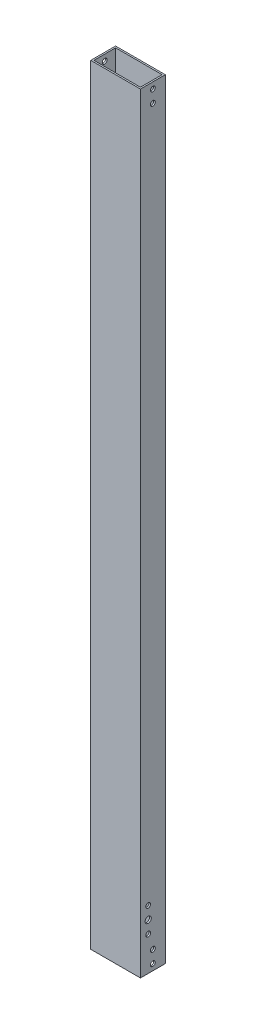
SolidWorks part; units mm, degrees
ref_plane "Front Plane" through (0, 0, 0) normal (0, 0, 1) x (1, 0, 0)
ref_plane "Top Plane" through (0, 0, 0) normal (0, 1, 0) x (1, 0, 0)
ref_plane "Right Plane" through (0, 0, 0) normal (1, 0, 0) x (0, 0, -1)
sketch "Sketch1" plane through (0, 0, 0) normal (0, 0, 1) x (1, 0, 0)
  line L1 (-25.4, -393.7) -> (25.4, -393.7)
  line L2 (-25.4, -393.7) -> (-25.4, 393.7)
  line L3 (-25.4, 393.7) -> (25.4, 393.7)
  line L4 (25.4, -393.7) -> (25.4, 393.7)
  line L5 (-25.4, -393.7) -> (25.4, 393.7) construction
  line L6 (-25.4, 393.7) -> (25.4, -393.7) construction
  point P0 (0, 0)
  dimension "D1" = 50.8
  dimension "D2" = 787.4
extrude "Boss-Extrude1" add sketch "Sketch1" along normal mid plane 25.4
shell "Shell1" thickness 1.5875 removed face at (0, -393.7, 0) removed face at (0, 393.7, 0)
sketch "Sketch3" plane through (0, 0, 0) normal (1, 0, 0) x (0, 0, -1)
  line L0 (-12.7, -393.7) -> (12.7, -393.7) construction
  circle A0 centre (0, -387.35) radius 2.4892
  circle A1 centre (0, -374.65) radius 2.4892
  point P6 (0, -393.7)
  dimension "D1" = 4.9784
  dimension "D2" = 6.35
  dimension "D3" = 12.7
extrude "Cut-Extrude1" cut sketch "Sketch3" against normal through all both and the other way through all
sketch "Sketch4" plane through (0, 0, 0) normal (1, 0, 0) x (0, 0, -1)
  line L4 (-12.7, -393.7) -> (12.7, -393.7) construction
  line L5 (-12.7, 393.7) -> (-12.7, -393.7) construction
  circle A3 centre (-4.7625, -346.075) radius 3.175
  circle A4 centre (-4.7625, -333.375) radius 2.4892
  circle A5 centre (-4.7625, -358.775) radius 2.4892
  point P16 (-7.9085, -337.088)
  dimension "D7" = 6.35
  dimension "D8" = 4.9784
  dimension "D9" = 12.7
  dimension "D10" = 12.7
  dimension "D11" = 47.625
  dimension "D12" = 7.9375
extrude "Cut-Extrude2" cut sketch "Sketch4" against normal through all both and the other way through all
mirror "Mirror1" about plane through (0, 0, 0) normal (0, 1, 0) of "Cut-Extrude1"
